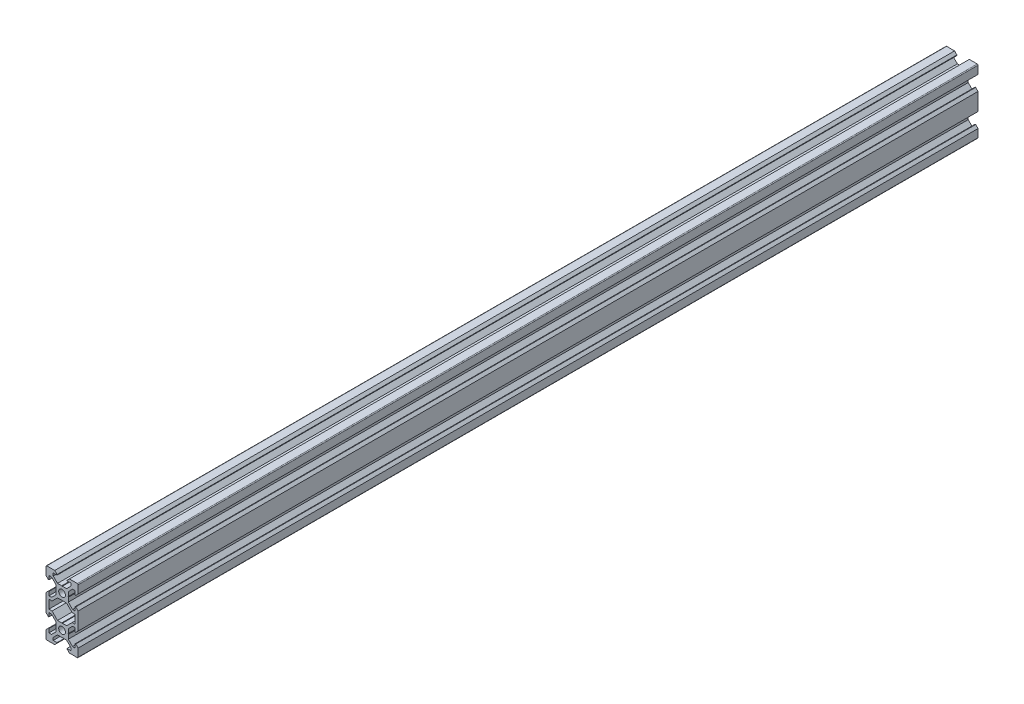
SolidWorks part; units mm, degrees
ref_plane "Plan de face" through (0, 0, 0) normal (0, 0, 1) x (1, 0, 0)
ref_plane "Plan de dessus" through (0, 0, 0) normal (0, 1, 0) x (1, 0, 0)
ref_plane "Plan de droite" through (0, 0, 0) normal (1, 0, 0) x (0, 0, -1)
ref_axis "Axe" through (0, 0, -13.782) along (0, 0, 1)
sketch "Esquisse1" plane through (0, 0, 0) normal (0, 0, 1) x (1, 0, 0)
  line L0 (0, 22.8977) -> (0, -22.8977) construction
  line L1 (-33.6074, 0) -> (33.6074, 0) construction
  line L2 (0, 0) -> (-22.2114, 22.2114) construction
  line L3 (-9.5, 10) -> (-4.58, 10)
  line L4 (-4.58, 10) -> (-3.125, 8.545)
  line L5 (-3.125, 8.545) -> (-3.125, 8.2)
  line L6 (-3.125, 8.2) -> (-5.5, 8.2)
  line L7 (-2.8393, 3.9) -> (-5.5, 6.5607)
  line L8 (-2.8393, 3.9) -> (-0.21, 3.9)
  line L9 (-5.5, 6.5607) -> (-5.5, 8.2)
  line L10 (0, 3.69) -> (0, 2.1)
  line L11 (-3.9, 2.8393) -> (-6.5607, 5.5)
  line L12 (-8.545, 3.125) -> (-8.2, 3.125)
  line L13 (-8.2, 3.125) -> (-8.2, 5.5)
  line L14 (-6.5607, 5.5) -> (-8.2, 5.5)
  line L15 (-10, 4.58) -> (-8.545, 3.125)
  line L16 (-10, 9.5) -> (-10, 4.58)
  line L17 (-0.21, 3.9) -> (0, 3.69)
  line L18 (-3.9, 2.8393) -> (-3.9, 0.21)
  line L20 (-3.9, 0.21) -> (-3.69, 0)
  line L21 (-0.21, -3.9) -> (0, -3.69)
  line L22 (0, -3.69) -> (0, -2.1)
  line L23 (-6.5607, -5.5) -> (-8.2, -5.5)
  line L24 (-2.8393, -3.9) -> (-0.21, -3.9)
  line L25 (-8.545, -3.125) -> (-8.2, -3.125)
  line L26 (-10, -4.58) -> (-8.545, -3.125)
  line L27 (-8.2, -3.125) -> (-8.2, -5.5)
  line L28 (-2.8393, -3.9) -> (-6.2393, -7.3)
  line L29 (-3.9, -2.8393) -> (-6.5607, -5.5)
  line L30 (-3.9, -2.8393) -> (-3.9, -0.21)
  line L31 (-3.9, -0.21) -> (-3.69, 0)
  line L32 (-6.2393, -7.3) -> (-8.2, -7.3)
  line L33 (-8.2, -7.3) -> (-8.2, -10)
  line L34 (-8.2, -10) -> (-10, -10)
  line L35 (-10, -10) -> (-10, -4.58)
  arc A0 (0, -2.1) -> (0, 2.1) centre (0, 0) cw
  arc A1 (-9.5, 10) -> (-10, 9.5) centre (-9.5, 9.5) ccw
  point P4 (0, 0)
  point P7 (0, 0)
  point P30 (-10, 10)
  dimension "D5" = 11
  dimension "D2" = 2.1
  dimension "D3" = 6.25
  dimension "D10" = 0.5
  dimension "D4" = 9.16
  dimension "D6" = 1.5
  dimension "D7" = 1.8
  dimension "D8" = 4.3
  dimension "D9" = 20
  dimension "D11" = 0.42
  dimension "D12" = 10
  dimension "D13" = 1.8
extrude "Boss.-Extru.1" add sketch "Esquisse1" along normal blind 560.3
sketch "Esquisse3" plane through (0, 0, 560.3) normal (0, 0, 1) x (1, 0, 0)
  line L0 (0, 0) -> (-9.8536, 9.8536) construction
  line L1 (-8.2, 8.2) -> (-8.2, 6.57)
  line L2 (-8.2, 6.57) -> (-7.54, 6.57)
  line L3 (-7.54, 6.57) -> (-6.57, 7.54)
  line L4 (-8.2, 3.125) -> (-8.2, 5.5) construction
  line L5 (-6.57, 8.2) -> (-6.57, 7.54)
  line L6 (-8.2, 8.2) -> (-6.57, 8.2)
  line L7 (-5.5, 6.5607) -> (-5.5, 8.2) construction
  arc A0 (-9.5, 10) -> (-10, 9.5) centre (-9.5, 9.5) ccw construction
  point P13 (-7.055, 7.055)
  point P14 (-6.57, 7.87)
  dimension "D1" = 1.07
extrude "Enlèv. mat.-Extru.1" [suppressed] cut sketch "Esquisse3" against normal through all
mirror "Symétrie1" about plane through (0, 3.69, 560.3) normal (-1, 0, 0) of "Enlèv. mat.-Extru.1", "Boss.-Extru.1"
mirror "Symétrie6" about plane through (-8.2, -10, 560.3) normal (0, 1, 0) of "Symétrie1", "Boss.-Extru.1"
